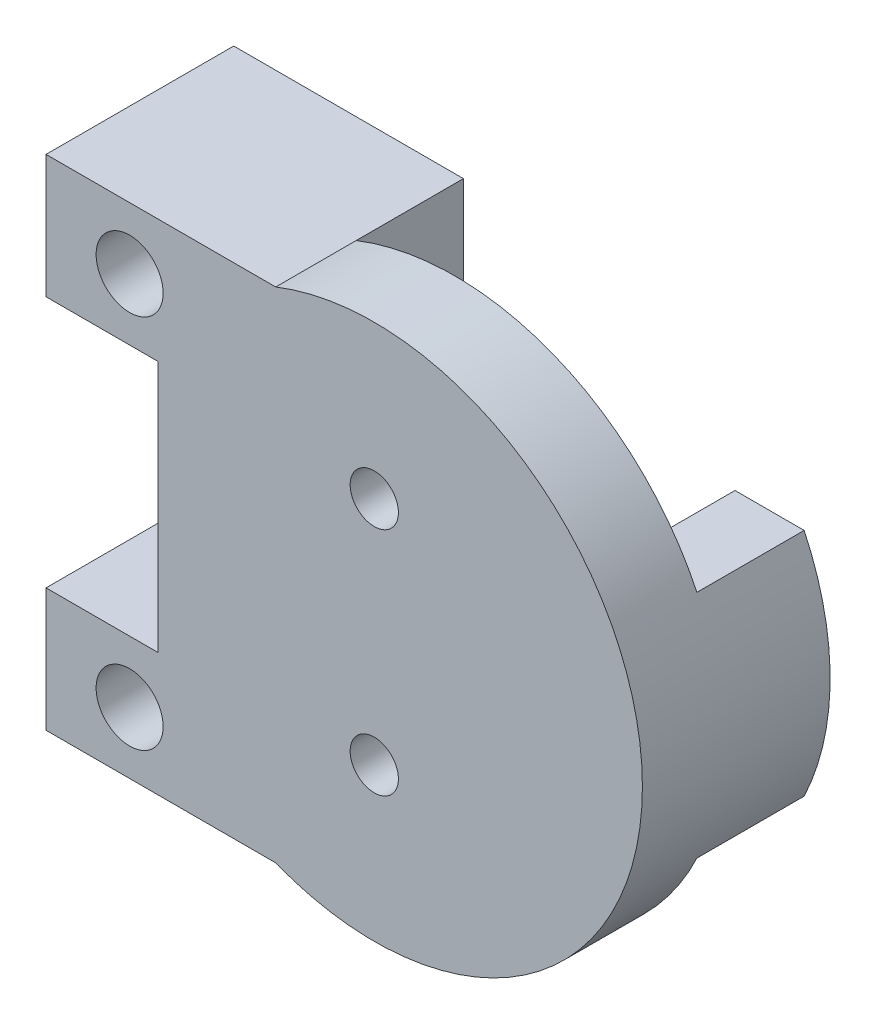
SolidWorks part; units mm, degrees
ref_plane "Front Plane" through (0, 0, 0) normal (0, 0, 1) x (1, 0, 0)
ref_plane "Top Plane" through (0, 0, 0) normal (0, 1, 0) x (1, 0, 0)
ref_plane "Right Plane" through (0, 0, 0) normal (1, 0, 0) x (0, 0, -1)
sketch "草图1" plane through (0, 0, 0) normal (0, 0, 1) x (1, 0, 0)
  line L15 (-25.7592, 31.7878) -> (-25.7592, 23.9878) construction
  line L16 (-25.7592, 23.9878) -> (-15.2592, 23.9878) construction
  line L17 (-15.2592, 23.9878) -> (-15.2592, 31.7878) construction
  line L18 (-15.2592, 31.7878) -> (-25.7592, 31.7878) construction
  line L19 (-25.7592, 31.7878) -> (-15.2592, 23.9878) construction
  line L20 (-15.2592, 31.7878) -> (-25.7592, 23.9878) construction
  line L21 (-28.7353, 20.8878) -> (-28.7353, 34.8878) construction
  line L24 (-19.6111, 32.1878) -> (-19.6111, 23.5878) construction
  line L25 (-16.6456, 27.8878) -> (-23.2139, 27.8878) construction
  line L35 (-23.2867, 37.1878) -> (-31.8521, 37.1878)
  line L36 (-31.8521, 37.1878) -> (-31.8521, 32.5878)
  line L38 (-31.8521, 23.1878) -> (-31.8521, 18.5878)
  line L39 (-31.8521, 18.5878) -> (-23.2867, 18.5878)
  line L41 (-31.8521, 32.5878) -> (-27.6691, 32.5878)
  line L42 (-27.6691, 32.5878) -> (-27.6691, 23.1878)
  line L43 (-27.6691, 23.1878) -> (-31.8521, 23.1878)
  circle A17 centre (-28.7353, 20.8878) radius 1.25
  circle A18 centre (-28.7353, 34.8878) radius 1.25
  circle A20 centre (-25.7592, 31.7878) radius 1.4
  circle A21 centre (-25.7592, 23.9878) radius 1.4
  circle A22 centre (-15.2592, 23.9878) radius 1.4
  circle A23 centre (-19.6111, 27.8878) radius 11.5 construction
  circle A26 centre (-15.2592, 31.7878) radius 1.4
  circle A27 centre (-19.6111, 32.1878) radius 0.9
  circle A28 centre (-19.6111, 23.5878) radius 0.9
  arc A29 (-23.2867, 18.5878) -> (-23.2867, 37.1878) centre (-19.6111, 27.8878) ccw
  point P1 (-19.6111, 27.8878)
  point P2 (-23.2139, 37.2066)
  point P12 (-20.5092, 27.8878)
  point P20 (-32.2489, 23.1878)
  point P26 (-20.5092, 27.8878)
  point P32 (-32.2489, 23.1878)
  point P33 (0, 0)
  point P34 (-32.2489, 37.1878)
  point P35 (-32.2489, 32.5878)
  point P36 (-32.2489, 32.8289)
  point P37 (-32.4775, 23.1878)
  point P38 (-32.9189, 18.5878)
  point P39 (-31.8521, 18.5878)
  dimension "D5" = 2.5
  dimension "D6" = 2.5
  dimension "D4" = 2.3
  dimension "D8" = 1.8
  dimension "D9" = 2.8
  dimension "D2" = 1.8
  dimension "D10" = 2.8
  dimension "D3" = 10
  dimension "D7" = 2.8
  dimension "D13" = 23
  dimension "D15" = 7.8
  dimension "D12" = 10.5
  dimension "D11" = 2.3
  dimension "D14" = 14
  dimension "D16" = 4.3
  dimension "D17" = 4.3
  dimension "D18" = 2.3
extrude "凸台-拉伸1" add sketch "草图1" along normal blind 3 contours A17 | A18 | A27 | A28 | L39 A29 L35 L36 L41 L42 L43 L38
extrude "凸台-拉伸2" add sketch "草图1<3>" against normal blind 1 contours A20 | A21 | A22 | A26
sketch "草图1<3>" plane through (0, 0, 0) normal (0, 0, 1) x (1, 0, 0) same geometry as "草图1"
sketch "草图2" plane through (0, 0, 0) normal (0, 0, -1) x (-1, 0, 0)
  line L0 (31.8521, 23.1878) -> (23.2867, 23.1878)
  line L5 (23.2867, 23.1878) -> (23.2867, 18.5878)
  line L11 (31.8521, 32.5878) -> (31.8521, 37.1878)
  line L12 (31.8521, 37.1878) -> (23.2867, 37.1878)
  line L13 (23.2867, 37.1878) -> (23.2867, 32.5878)
  line L14 (23.2867, 32.5878) -> (31.8521, 32.5878)
  line L15 (23.2867, 18.5878) -> (31.8521, 18.5878)
  line L16 (31.8521, 18.5878) -> (31.8521, 23.1878)
  line L17 (10.579, 32.1796) -> (13.158, 32.1796)
  line L18 (10.579, 23.5959) -> (13.158, 23.5959)
  circle A0 centre (28.7353, 20.8878) radius 1.25
  circle A2 centre (19.6111, 27.8878) radius 7.75 construction
  arc A3 (10.579, 32.1796) -> (10.579, 23.5959) centre (19.6111, 27.8878) ccw
  circle A4 centre (28.7353, 34.8878) radius 1.25
  arc A5 (23.2867, 37.1878) -> (23.2867, 18.5878) centre (19.6111, 27.8878) ccw construction
  arc A6 (13.158, 23.5959) -> (13.158, 32.1796) centre (19.6111, 27.8878) cw
  dimension "D1" = 15.5
extrude "凸台-拉伸3" add sketch "草图2" along normal blind 4
